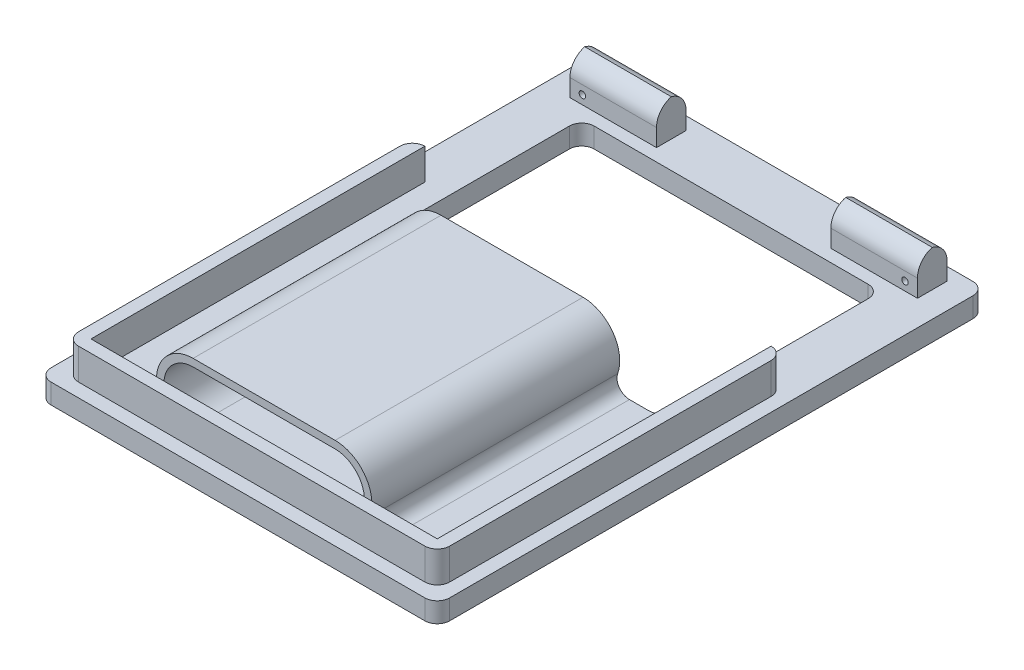
SolidWorks part; units mm, degrees
ref_plane "Front Plane" through (0, 0, 0) normal (0, 0, 1) x (1, 0, 0)
ref_plane "Top Plane" through (0, 0, 0) normal (0, 1, 0) x (1, 0, 0)
ref_plane "Right Plane" through (0, 0, 0) normal (1, 0, 0) x (0, 0, -1)
sketch "Sketch3" plane through (0, 0, 0) normal (0, 1, 0) x (1, 0, 0)
  line L0 (-75, 110) -> (75, 110)
  line L1 (-75, -105) -> (75, -105)
  line L2 (-75, -105) -> (-75, 105)
  line L4 (75, -105) -> (75, 105)
  line L5 (-75, -105) -> (75, 105) construction
  line L6 (-75, 105) -> (75, -105) construction
  line L7 (80, -105) -> (80, 105)
  line L8 (-75, -110) -> (75, -110)
  line L9 (-80, -105) -> (-80, 105)
  line L10 (-80, -110) -> (80, -110) construction
  line L11 (-80, -110) -> (-80, 110) construction
  line L12 (80, -110) -> (80, 110) construction
  line L13 (-80, 110) -> (80, 110) construction
  line L15 (-75, 105) -> (75, 105)
  line L19 (-75, 105) -> (75, 105) construction
  line L20 (-69.75, 104.9) -> (69.75, 104.9)
  line L21 (-69.75, 104.9) -> (-69.75, 93)
  line L22 (-69.75, 93) -> (69.75, 93)
  line L23 (69.75, 104.9) -> (69.75, 93)
  arc A0 (-75, -110) -> (-80, -105) centre (-75, -105) cw
  arc A1 (80, -105) -> (75, -110) centre (75, -105) cw
  arc A2 (75, 110) -> (80, 105) centre (75, 105) cw
  arc A3 (-75, 110) -> (-80, 105) centre (-75, 105) ccw
  point P0 (0, 0)
  point P5 (0, 93)
  point P22 (0, 0)
  point P24 (-69.75, 101.471)
  dimension "D4" = 5
  dimension "D1" = 75
  dimension "D2" = 210
  dimension "D5" = 11.9
  dimension "D6" = 139.5
  dimension "D7" = 0.1
  dimension "D3" = 5
extrude "Boss-Extrude1" add sketch "Sketch3" along normal blind 8 contours L1 L4 L2 | L0 A3 L9 A0 L8 A1 L7 A2 L4 L1 L2 | L2 L4 | L23 L15 L21 L22 region at (0, 0, -107.2797) region at (0, 0, 5.5048) region at (0, 0, -98.95)
extrude "Boss-Extrude2" add sketch "Sketch3<7>" along normal blind 15 from surface contours L23 L15 L21 L22 region at (0, 0, -98.95) starting at face at (0, 8, 0)
sketch "Sketch3<7>" plane through (0, 0, 0) normal (0, 1, 0) x (1, 0, 0) same geometry as "Sketch3"
fillet "Fillet1" radius 8 2 edges at (0, 23, -93) (0, 23, -104.9)
sketch "Sketch4" plane through (0, 0, 0) normal (0, -1, 0) x (1, 0, 0)
  line L0 (69.75, -93) -> (-69.75, -93) construction
  line L1 (-55, 0) -> (55, 0)
  line L2 (-60, -5) -> (-60, -83)
  line L3 (-55, -88) -> (55, -88)
  line L4 (60, -5) -> (60, -83)
  line L5 (-75, 110) -> (75, 110) construction
  line L6 (80, 105) -> (80, -105) construction
  arc A0 (-55, 0) -> (-60, -5) centre (-55, -5) ccw
  arc A1 (-60, -83) -> (-55, -88) centre (-55, -83) ccw
  arc A2 (55, -88) -> (60, -83) centre (55, -83) ccw
  arc A3 (55, 0) -> (60, -5) centre (55, -5) cw
  point P4 (0, -88)
  dimension "D4" = 5
  dimension "D1" = 5
  dimension "D2" = 110
  dimension "D3" = 20
extrude "Cut-Extrude1" cut sketch "Sketch4" against normal up to next
sketch "Sketch5" plane through (0, 8, 0) normal (0, 1, 0) x (1, 0, 0)
  line L0 (75, -105) -> (75, 105) construction
  line L1 (-75, -105) -> (75, -105) construction
  line L2 (-75, -105) -> (-75, 105) construction
  line L3 (-75, 105) -> (75, 105) construction
  line L4 (75, 110) -> (-75, 110)
  line L5 (80, -105) -> (80, 105)
  line L6 (-75, -110) -> (75, -110)
  line L7 (-80, 105) -> (-80, -105)
  line L8 (75, 110) -> (-75, 110)
  line L9 (80, -105) -> (80, 105)
  line L10 (-75, -110) -> (75, -110)
  line L11 (-80, 105) -> (-80, -105)
  line L12 (69.75, 104.9) -> (-69.75, 104.9)
  line L13 (-69.75, 104.9) -> (-69.75, 93)
  line L14 (-69.75, 93) -> (69.75, 93)
  line L15 (69.75, 93) -> (69.75, 104.9)
  line L16 (69.75, 104.9) -> (-69.75, 104.9)
  line L17 (-69.75, 104.9) -> (-69.75, 93)
  line L18 (-69.75, 93) -> (69.75, 93)
  line L19 (69.75, 93) -> (69.75, 104.9)
  line L20 (75, -105) -> (75, 105)
  line L21 (-75, -105) -> (75, -105)
  line L22 (-75, -105) -> (-75, 105)
  line L23 (-75, 105) -> (75, 105)
  line L24 (-75, 35) -> (75, 35)
  line L25 (-69.5, 34.5) -> (-69.5, -99.5)
  line L26 (-69.5, -104.5) -> (69.5, -104.5)
  line L27 (-74.5, -99.5) -> (-74.5, 29.5)
  line L28 (-69.5, 34.5) -> (69.5, 34.5)
  line L29 (74.5, -99.5) -> (74.5, 29.5)
  line L30 (-69.5, -99.5) -> (69.5, -99.5)
  line L31 (69.5, -99.5) -> (69.5, 34.5)
  arc A0 (-74.5, 29.5) -> (-69.5, 34.5) centre (-69.5, 29.5) cw
  arc A1 (69.5, 34.5) -> (74.5, 29.5) centre (69.5, 29.5) cw
  arc A2 (69.5, -104.5) -> (74.5, -99.5) centre (69.5, -99.5) ccw
  arc A3 (-69.5, -104.5) -> (-74.5, -99.5) centre (-69.5, -99.5) cw
  arc A4 (80, 105) -> (75, 110) centre (75, 105) ccw
  arc A5 (75, -110) -> (80, -105) centre (75, -105) ccw
  arc A6 (-80, -105) -> (-75, -110) centre (-75, -105) ccw
  arc A7 (-75, 110) -> (-80, 105) centre (-75, 105) ccw
  arc A8 (80, 105) -> (75, 110) centre (75, 105) ccw
  arc A9 (75, -110) -> (80, -105) centre (75, -105) ccw
  arc A10 (-80, -105) -> (-75, -110) centre (-75, -105) ccw
  arc A11 (-75, 110) -> (-80, 105) centre (-75, 105) ccw
  point P26 (0, -104.5)
  point P42 (0, -99.5)
  dimension "D7" = 5
  dimension "D3" = 75
  dimension "D4" = 0.5
  dimension "D5" = 0.5
  dimension "D6" = 0.5
  dimension "D8" = 5
  dimension "D9" = 5
  dimension "D1" = 0
  dimension "D2" = 0
extrude "Boss-Extrude3" add sketch "Sketch5" along normal blind 12.5 contours A3 L26 A2 L29 A1 L31 L30 L25 A0 L27 region at (-71.5377, 8, 32.5)
sketch "Sketch6" plane through (0, 0, -104.9) normal (0, 0, -1) x (-1, 0, 0)
  line L0 (-69.75, 15) -> (-69.75, 8) construction
  line L1 (0, 0) -> (0, 22.7329) construction
  line L2 (-69.75, 22.7329) -> (69.75, 22.7329) construction
  circle A0 centre (-64.75, 11.5) radius 1.3
  circle A1 centre (64.75, 11.5) radius 1.3
  point P5 (-69.75, 11.5)
  dimension "D1" = 2.6
  dimension "D2" = 5
extrude "Cut-Extrude2" cut sketch "Sketch6" against normal up to next
sketch "Sketch8" plane through (0, 0, 99.5) normal (0, 0, -1) x (-1, 0, 0)
  line L0 (-28.5, 19.5) -> (28.5, 19.5) construction
  line L1 (-28.5, 31) -> (28.5, 31)
  line L2 (-28.5, 8) -> (28.5, 8)
  line L3 (69.5, 8) -> (-69.5, 8) construction
  line L4 (0, 19.5) -> (0, 0) construction
  line L5 (-28.5, 31.25) -> (28.5, 31.25)
  line L6 (-28.5, 7.75) -> (28.5, 7.75)
  line L7 (-28.5, 34.25) -> (28.5, 34.25)
  line L8 (-28.5, 4.75) -> (28.5, 4.75)
  line L9 (-37.7365, 8) -> (37.7365, 8)
  arc A0 (-28.5, 31) -> (-28.5, 8) centre (-28.5, 19.5) ccw
  arc A1 (28.5, 8) -> (28.5, 31) centre (28.5, 19.5) ccw
  arc A2 (28.5, 7.75) -> (28.5, 31.25) centre (28.5, 19.5) ccw
  arc A3 (-28.5, 31.25) -> (-28.5, 7.75) centre (-28.5, 19.5) ccw
  arc A4 (28.5, 4.75) -> (28.5, 34.25) centre (28.5, 19.5) ccw
  arc A5 (-28.5, 34.25) -> (-28.5, 4.75) centre (-28.5, 19.5) ccw
  point P2 (0, 19.5)
  line M6 (-69.5, 8) -> (69.5, 8)
  line M8 (69.5, 20.5) -> (-69.5, 20.5)
  dimension "D2" = 80
  dimension "D1" = 23
  dimension "D3" = 0.25
  dimension "D4" = 3
extrude "Boss-Extrude4" add sketch "Sketch8" along normal up to surface (99.5 mm away) contours L7 A5 A3 L5 A2 A4 M8 | L9 A4 A2 M8 | A5 A3 M8 M6 region at (41.7117, 21.3752, 99.5) region at (39.4576, 13.5579, 99.5) region at (-39.4576, 13.5579, 99.5) up to face at (0, 4, 0)
fillet "Fillet2" radius 5 2 edges at (-37.7365, 8, 49.75) (37.7365, 8, 49.75)
sketch "Sketch9" plane through (0, 8, 0) normal (0, 1, 0) x (1, 0, 0)
  line L0 (69.75, 98.95) -> (-69.75, 98.95) construction
  line L1 (-35, 104.9) -> (35, 104.9)
  line L2 (-35, 104.9) -> (-35, 93)
  line L3 (-35, 93) -> (35, 93)
  line L4 (35, 104.9) -> (35, 93)
  line L5 (-35, 104.9) -> (35, 93) construction
  line L6 (-35, 93) -> (35, 104.9) construction
  line L7 (69.75, 93) -> (-69.75, 93) construction
  point P0 (0, 98.95)
  dimension "D1" = 70
extrude "Cut-Extrude3" cut sketch "Sketch9" along normal up to next
